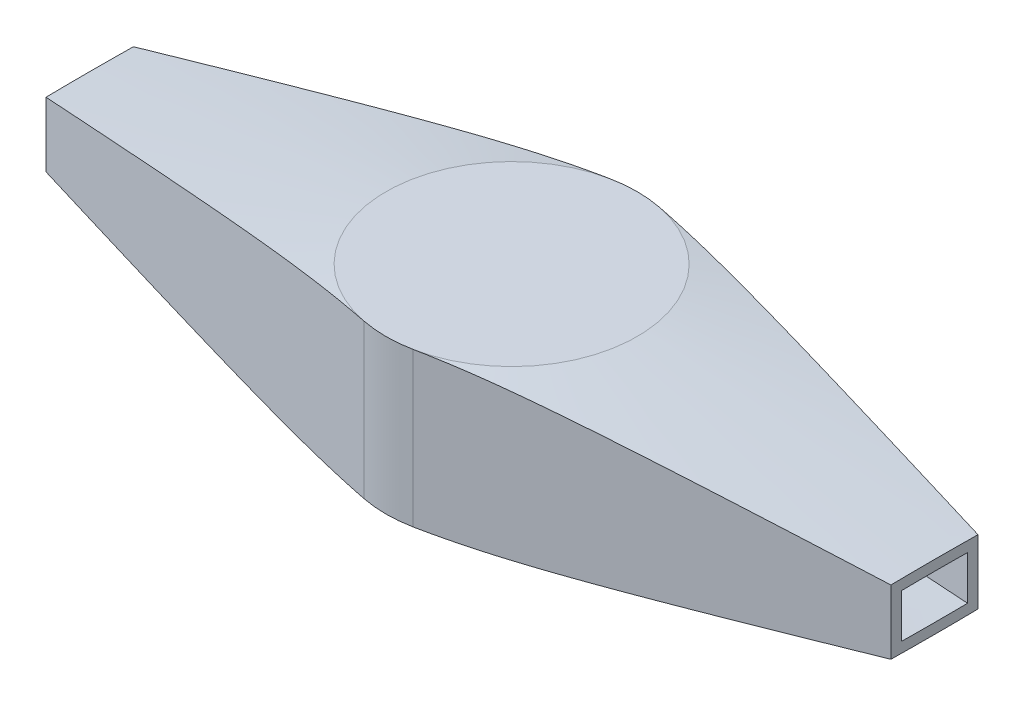
SolidWorks part; units mm, degrees
note: The reader was unsure of these and kept them because the rebuilt part matched: shared geometry of "草图16<5>".
other "相机2"
other "相机3"
material "PEN"
ref_plane "前视基准面" through (0, 0, 0) normal (0, 0, 1) x (1, 0, 0)
ref_plane "上视基准面" through (0, 0, 0) normal (0, 1, 0) x (1, 0, 0)
ref_plane "右视基准面" through (0, 0, 0) normal (1, 0, 0) x (0, 0, -1)
sketch "草图1" plane through (0, 0, 0) normal (0, 1, 0) x (1, 0, 0)
  circle A0 centre (0, 0) radius 49
extrude "凸台-拉伸1" add sketch "草图1" along normal mid plane 60
sketch "草图2" plane through (0, 0, 0) normal (0, 1, 0) x (1, 0, 0)
  line L8 (0, 0) -> (165, 0)
  line L9 (0, 0) -> (-164.6213, 0)
  line L11 (165, 0) -> (165, 16.9895)
  line L16 (165, 0) -> (165, -16.9895)
  line L17 (-164.6213, 0) -> (-164.6213, 17.0652)
  line L18 (-164.6213, 0) -> (-164.6213, -17.0652)
  line L21 (-250, 0) -> (-9.604, 48.0496)
  line L22 (-250, 0) -> (-9.604, -48.0496)
  line L23 (250, 0) -> (9.604, -48.0496)
  line L24 (250, 0) -> (9.604, 48.0496)
  circle A2 centre (0, 0) radius 49 construction
  arc A3 (-9.604, 48.0496) -> (9.604, 48.0496) centre (0, 0) cw
  arc A4 (-9.604, -48.0496) -> (9.604, -48.0496) centre (0, 0) ccw
sketch "草图14" plane through (0, 0, 0) normal (0, 1, 0) x (1, 0, 0)
  line L5 (-250, 0) -> (-9.604, -48.0496)
  line L6 (250, 0) -> (9.604, -48.0496) construction
  line L7 (9.604, -48.0496) -> (250, 0)
  line L8 (250, 0) -> (9.604, 48.0496)
  line L9 (-9.604, 48.0496) -> (-250, 0)
  arc A2 (-9.604, -48.0496) -> (9.604, -48.0496) centre (0, 0) ccw
  arc A3 (9.604, 48.0496) -> (-9.604, 48.0496) centre (0, 0) ccw
  arc A4 (9.604, 48.0496) -> (-9.604, 48.0496) centre (0, 0) ccw construction
sketch "草图15" plane through (0, 0, 0) normal (0, 1, 0) x (1, 0, 0)
  line L6 (-9.604, -48.0496) -> (-164.6213, -17.0652)
  line L7 (-164.6213, -17.0652) -> (-164.6213, 17.0652)
  line L8 (-164.6213, 17.0652) -> (-9.604, 48.0496)
  line L9 (9.604, 48.0496) -> (165, 16.9895)
  line L10 (165, 16.9895) -> (165, -16.9895)
  line L11 (165, -16.9895) -> (9.604, -48.0496)
  line L12 (250, 0) -> (9.604, -48.0496) construction
  circle A0 centre (0, 0) radius 49 construction
  arc A2 (-9.604, 48.0496) -> (9.604, 48.0496) centre (0, 0) cw
  arc A3 (9.604, 48.0496) -> (-9.604, 48.0496) centre (0, 0) ccw construction
  arc A4 (9.604, -48.0496) -> (-9.604, -48.0496) centre (0, 0) cw
  arc A5 (-9.604, -48.0496) -> (9.604, -48.0496) centre (0, 0) ccw construction
sketch "草图16" plane through (0, 0, 0) normal (0, 1, 0) x (1, 0, 0)
  circle A0 centre (0, 0) radius 250
  circle A1 centre (0, 0) radius 49 construction
loft "放样1" add profiles "草图16" section "草图16" section edge at (0, 30, 49) connector at (-249.9996, 0, 0.4697) connector at (-48.9999, 30, -0.0701)
loft "放样3" add profiles "草图16<5>" section "草图16<5>" section edge at (0, -30, 49) connector at (-250, 0, -0.0114) connector at (-49, -30, 0.0574)
sketch "草图16<5>" plane through (0, 0, 0) normal (0, 1, 0) x (1, 0, 0) same geometry as "草图16"
extrude "切除-拉伸1" cut sketch "草图14" against normal through all both and the other way through all flip side to cut
shell "抽壳1" thickness 4
extrude "切除-拉伸2" cut sketch "草图15" against normal through all both and the other way through all flip side to cut
sketch "草图17" plane through (0, 0, 0) normal (0, 1, 0) x (1, 0, 0)
  line L0 (-9.604, 48.0496) -> (-9.604, -48.0496)
  line L1 (-164.6213, 17.0652) -> (-164.6213, -17.0652)
  line L2 (-164.6213, 0) -> (-9.604, 0)
  arc A0 (-9.604, -48.0496) -> (9.604, -48.0496) centre (0, 0) ccw construction
  arc A1 (-9.6045, 48.0495) -> (-9.604, -48.0496) centre (0, 0) ccw construction
sketch "草图20" plane through (0, 26, 0) normal (0, -1, 0) x (-1, 0, 0)
  line L0 (8.7458, 44.1066) -> (8.7458, -43.7451)
  line L1 (8.7458, 0.1808) -> (164.6213, 0)
  line L2 (164.6213, -17.0652) -> (164.6213, 17.0652) construction
  line L3 (164.6213, -12.9861) -> (164.6213, 12.9861)
  line L4 (164.6213, 0) -> (134.6214, 0.0348)
